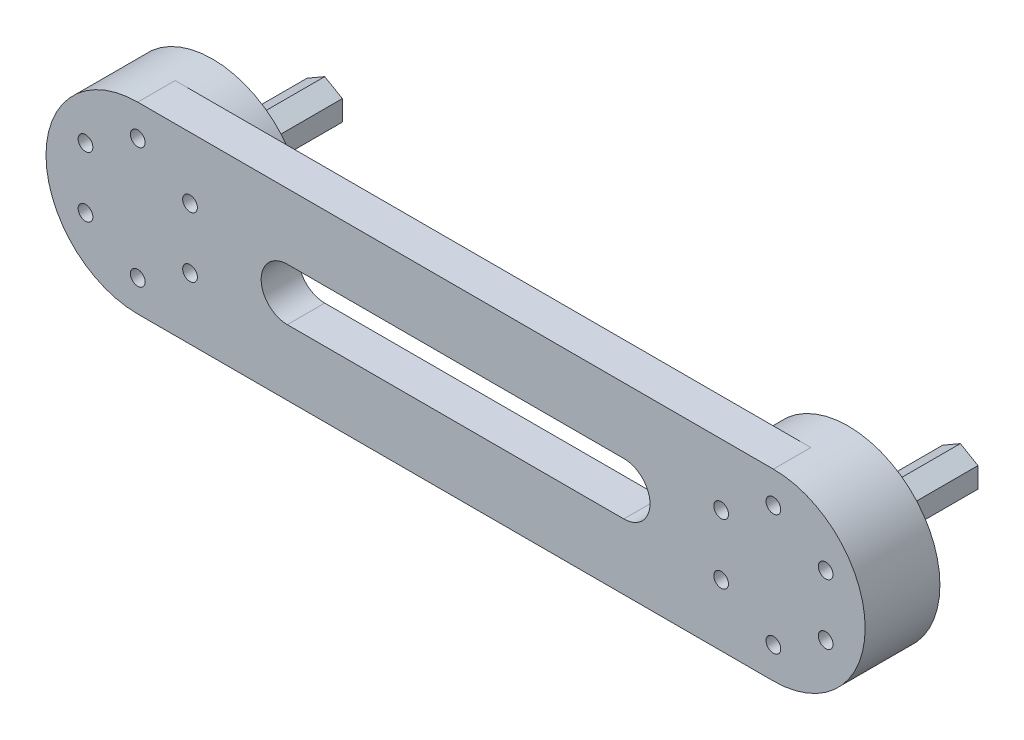
SolidWorks part; units mm, degrees
ref_plane "Front Plane" through (0, 0, 0) normal (0, 0, 1) x (1, 0, 0)
ref_plane "Top Plane" through (0, 0, 0) normal (0, 1, 0) x (1, 0, 0)
ref_plane "Right Plane" through (0, 0, 0) normal (1, 0, 0) x (0, 0, -1)
sketch "Sketch1" plane through (0, 0, 0) normal (0, 0, 1) x (1, 0, 0)
  line L0 (-86.7168, 15.1697) -> (-83.7168, 13.4376)
  line L1 (-83.7168, 13.4376) -> (-83.7168, 9.9735)
  line L2 (-83.7168, 9.9735) -> (-86.7168, 8.2415)
  line L3 (-86.7168, 8.2415) -> (-89.7168, 9.9735)
  line L4 (-89.7168, 9.9735) -> (-89.7168, 13.4376)
  line L5 (-89.7168, 13.4376) -> (-86.7168, 15.1697)
  line L6 (-86.7168, 27.2903) -> (21.2332, 27.2903)
  line L7 (-86.7168, -3.8792) -> (21.2332, -3.8792)
  line L9 (-61.3168, 16.1506) -> (-4.1668, 16.1506)
  line L10 (-61.3168, 7.2606) -> (-4.1668, 7.2606)
  line L11 (-32.7418, 16.1506) -> (-32.7418, 27.2903) construction
  line L12 (-32.7418, 7.2606) -> (-32.7418, -3.8792) construction
  line L13 (24.2332, 13.4376) -> (21.2332, 15.1697)
  line L14 (24.2332, 9.9735) -> (24.2332, 13.4376)
  line L15 (21.2332, 8.2415) -> (24.2332, 9.9735)
  line L16 (18.2332, 9.9735) -> (21.2332, 8.2415)
  line L17 (18.2332, 13.4376) -> (18.2332, 9.9735)
  line L18 (21.2332, 15.1697) -> (18.2332, 13.4376)
  circle A7 centre (-86.7168, 11.7056) radius 15.5847
  circle A8 centre (-86.7168, 21.9556) radius 1.25
  circle A9 centre (-95.5935, 16.8306) radius 1.25
  circle A10 centre (-95.5935, 6.5806) radius 1.25
  circle A11 centre (-86.7168, 1.4556) radius 1.25
  circle A12 centre (-77.84, 6.5806) radius 1.25
  circle A13 centre (-77.84, 16.8306) radius 1.25
  arc A14 (-86.7168, 27.2903) -> (-86.7168, -3.8792) centre (-86.7168, 11.7056) cw
  arc A16 (-61.3168, 16.1506) -> (-61.3168, 7.2606) centre (-61.3168, 11.7056) ccw
  arc A18 (-4.1668, 16.1506) -> (-4.1668, 7.2606) centre (-4.1668, 11.7056) cw
  arc A19 (21.2332, 27.2903) -> (21.2332, -3.8792) centre (21.2332, 11.7056) ccw
  circle A20 centre (12.3565, 16.8306) radius 1.25
  circle A21 centre (12.3565, 6.5806) radius 1.25
  circle A22 centre (21.2332, 1.4556) radius 1.25
  circle A23 centre (30.11, 6.5806) radius 1.25
  circle A24 centre (30.11, 16.8306) radius 1.25
  circle A25 centre (21.2332, 21.9556) radius 1.25
  circle A26 centre (21.2332, 11.7056) radius 15.5847
  point P0 (0, 0)
  point P9 (-32.7418, 7.2606)
  point P10 (-32.7418, 16.1506)
  point P19 (-32.7418, 11.7056)
  dimension "D5" = 4.445
  dimension "D6" = 12.3565
  dimension "D7" = 18.2332
  dimension "D16" = 31.1694
  dimension "D17" = 2.5
  dimension "D27" = 2.5
  dimension "D28" = 2.5
  dimension "D29" = 2.5
  dimension "D30" = 2.5
  dimension "D44" = 2.5
  dimension "D8" = 1.4556
  dimension "D9" = 28.575
  dimension "D10" = 25.4
  dimension "D15" = 10.25
  dimension "D18" = 83.7168
  dimension "D19" = 86.7168
  dimension "D20" = 3.4641
  dimension "D21" = 8.8768
  dimension "D22" = 8.2415
  dimension "D31" = 10.25
  dimension "D32" = 10.25
  dimension "D33" = 10.25
  dimension "D34" = 5.125
  dimension "D35" = 10.25
  dimension "D36" = 8.8768
  dimension "D37" = 10.25
  dimension "D39" = 8.8768
  dimension "D40" = 8.8768
  dimension "D41" = 25.4
extrude "Boss-Extrude5" add sketch "Sketch1" along normal blind 6.35 contours A19 L6 A7 L7 L9 A18 L10 A16 | A7 A13 A12 A11 A10 A9 A8 L4 L5 L0 L1 L2 L3 | A26 A19 A24 A22 A20 L18 L13 L14 L15 L16 L17 A21 A23 A25 region at (-32.7418, 26.1667, 0) region at (-76.0084, 22.4139, 0) region at (31.9416, 22.4139, 0)
extrude "Boss-Extrude6" add sketch "Sketch1<7>" against normal blind 6.35 contours A7 A13 A12 A11 A10 A9 A8 L4 L5 L0 L1 L2 L3 | A26 A19 A24 A22 A20 L18 L13 L14 L15 L16 L17 A21 A23 A25 region at (-76.0084, 22.4139, 0) region at (31.9416, 22.4139, 0)
sketch "Sketch1<7>" plane through (0, 0, 0) normal (0, 0, 1) x (1, 0, 0) same geometry as "Sketch1"
extrude "Boss-Extrude7" add sketch "Sketch1<8>" along normal blind 6.35 and the other way blind 25.4 contours L2 L3 L4 L5 L0 L1 | L15 L14 L13 L18 L17 L16
sketch "Sketch1<8>" plane through (0, 0, 0) normal (0, 0, 1) x (1, 0, 0) same geometry as "Sketch1"
